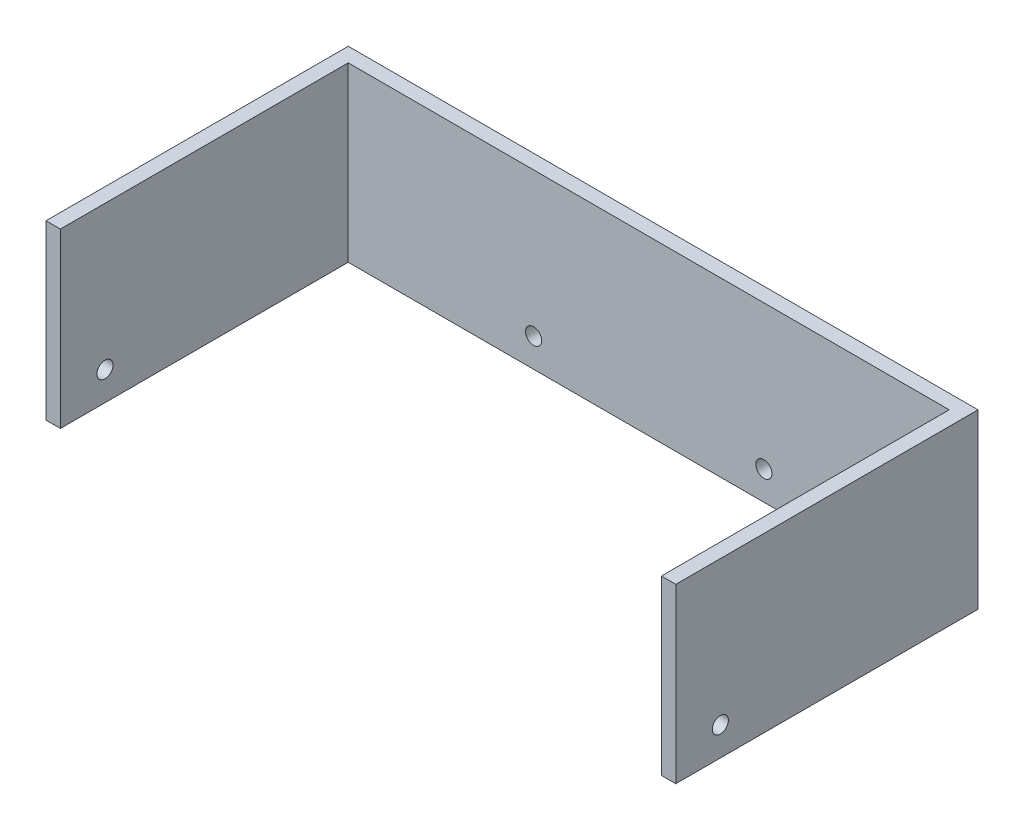
SolidWorks part; units mm, degrees
material "Copper"
ref_plane "Front Plane" through (0, 0, 0) normal (0, 0, 1) x (1, 0, 0)
ref_plane "Top Plane" through (0, 0, 0) normal (0, 1, 0) x (1, 0, 0)
ref_plane "Right Plane" through (0, 0, 0) normal (1, 0, 0) x (0, 0, -1)
sketch "Sketch1" plane through (0, 0, 0) normal (0, 0, 1) x (1, 0, 0)
  line L1 (0, 0) -> (-138.9256, 0)
  line L2 (0, 0) -> (0, -12.7)
  line L3 (0, -12.7) -> (-138.9256, -12.7)
  line L4 (-138.9256, 0) -> (-138.9256, -12.7)
  circle A0 centre (-94.8628, -6.35) radius 1.778
  circle A1 centre (-44.0628, -6.35) radius 1.778
  point P9 (-69.4628, 0)
  dimension "D3" = 3.556
  dimension "D4" = 3.556
  dimension "D5" = 6.35
  dimension "D1" = 138.9256
  dimension "D2" = 12.7
  dimension "D6" = 6.35
  dimension "D7" = 50.8
  dimension "D8" = 25.4
extrude "Boss-Extrude1" add sketch "Sketch1" along normal blind 3.175
sketch "Sketch2" plane through (0, 0, 3.175) normal (0, 0, 1) x (1, 0, 0)
  line L0 (-138.9256, -12.7) -> (0, -12.7) construction
  line L1 (-138.9256, 0) -> (-135.7506, 0)
  line L2 (-138.9256, 0) -> (-138.9256, -12.7)
  line L3 (-138.9256, -12.7) -> (-135.7506, -12.7)
  line L4 (-135.7506, 0) -> (-135.7506, -12.7)
  line L6 (0, 0) -> (-3.175, 0)
  line L7 (0, 0) -> (0, -12.7)
  line L8 (0, -12.7) -> (-3.175, -12.7)
  line L9 (-3.175, 0) -> (-3.175, -12.7)
  dimension "D1" = 3.175
  dimension "D2" = 3.175
extrude "Boss-Extrude2" add sketch "Sketch2" along normal blind 63.5
sketch "Sketch3" plane through (0, 0, 0) normal (1, 0, 0) x (0, 0, -1)
  line L0 (-66.675, 0) -> (0, 0) construction
  line L1 (0, -12.7) -> (0, 0) construction
  circle A0 centre (-56.8402, -6.35) radius 1.778
  dimension "D1" = 3.556
  dimension "D2" = 6.35
  dimension "D3" = 56.8402
extrude "Cut-Extrude1" cut sketch "Sketch3" against normal blind 152.4
sketch "Sketch4" plane through (0, 0, 0) normal (0, 1, 0) x (1, 0, 0)
  line L0 (-135.7506, -66.675) -> (-138.9256, -66.675)
  line L1 (-138.9256, -66.675) -> (-138.9256, 0)
  line L2 (-138.9256, 0) -> (0, 0)
  line L3 (-3.175, -66.675) -> (-3.175, -3.175)
  line L4 (-3.175, -3.175) -> (-135.7506, -3.175)
  line L5 (-135.7506, -3.175) -> (-135.7506, -66.675)
  line L6 (-3.175, -66.675) -> (0, -66.675)
  line L7 (0, -66.675) -> (0, 0)
extrude "Boss-Extrude3" add sketch "Sketch4" along normal blind 25.4
